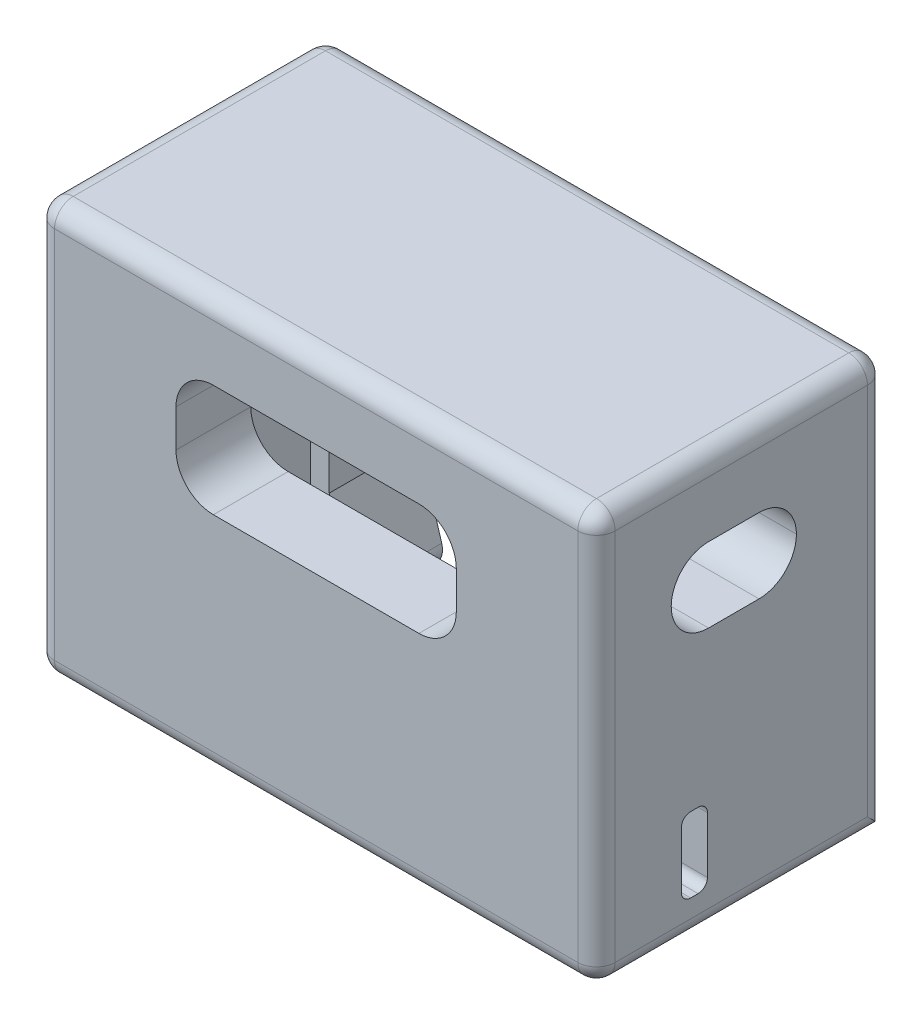
SolidWorks part; units mm, degrees
ref_plane "Front Plane" through (0, 0, 0) normal (0, 0, 1) x (1, 0, 0)
ref_plane "Top Plane" through (0, 0, 0) normal (0, 1, 0) x (1, 0, 0)
ref_plane "Right Plane" through (0, 0, 0) normal (1, 0, 0) x (0, 0, -1)
sketch "Sketch1" plane through (0, 0, 0) normal (0, 1, 0) x (1, 0, 0)
  line L1 (-19.05, 3.048) -> (19.05, 3.048)
  line L2 (-19.05, 3.048) -> (-19.05, -3.048)
  line L3 (-19.05, -3.048) -> (19.05, -3.048)
  line L4 (19.05, 3.048) -> (19.05, -3.048)
  line L5 (-19.05, 3.048) -> (19.05, -3.048) construction
  line L6 (-19.05, -3.048) -> (19.05, 3.048) construction
  point P0 (0, 0)
  dimension "D1" = 38.1
  dimension "D2" = 6.096
extrude "Boss-Extrude1" add sketch "Sketch1" along normal blind 22.86
sketch "Sketch4" plane through (0, 0, 0) normal (0, -1, 0) x (1, 0, 0)
  line L0 (19.05, -3.048) -> (-19.05, -3.048) construction
  line L1 (-12.7, 3.048) -> (12.7, 3.048)
  line L2 (-12.7, 3.048) -> (-12.7, -3.048)
  line L3 (-12.7, -3.048) -> (12.7, -3.048)
  line L4 (12.7, 3.048) -> (12.7, -3.048)
  line L5 (-12.7, 3.048) -> (12.7, -3.048) construction
  line L6 (-12.7, -3.048) -> (12.7, 3.048) construction
  point P0 (0, 0)
  dimension "D1" = 25.4
extrude "Cut-Extrude1" cut sketch "Sketch4" against normal blind 15.875
fillet "Fillet1" radius 1.27 1 edges at (0, 15.875, -3.048)
sketch "Sketch5" plane through (0, 22.86, 0) normal (0, 1, 0) x (1, 0, 0)
  line L1 (19.05, 3.048) -> (-19.05, 3.048)
  line L2 (19.05, 3.048) -> (19.05, -16.637)
  line L3 (19.05, -16.637) -> (-19.05, -16.637)
  line L4 (-19.05, 3.048) -> (-19.05, -16.637)
  dimension "D1" = 19.685
  dimension "D2" = 38.1
extrude "Boss-Extrude2" add sketch "Sketch5" along normal blind 5.08
sketch "Sketch6" plane through (0, 0, 3.048) normal (0, 0, 1) x (1, 0, 0)
  line L0 (-12.7, 0) -> (-10.668, 0)
  line L1 (-10.668, 0) -> (-12.7, 6.858)
  line L2 (-12.7, 15.875) -> (-12.7, 0) construction
  line L3 (-12.7, 6.858) -> (-12.7, 0)
  dimension "D1" = 2.032
  dimension "D2" = 6.858
extrude "Boss-Extrude3" add sketch "Sketch6" against normal up to surface (6.096 mm away) up to face at (0, 11.2713, -3.048)
sketch "Sketch7" plane through (0, 0, 3.048) normal (0, 0, 1) x (1, 0, 0)
  line L0 (12.7, 0) -> (10.668, 0)
  line L1 (10.668, 0) -> (12.7, 6.858)
  line L2 (12.7, 15.875) -> (12.7, 0) construction
  line L3 (12.7, 6.858) -> (12.7, 0)
  dimension "D1" = 2.032
  dimension "D2" = 6.858
extrude "Boss-Extrude4" add sketch "Sketch7" against normal up to surface (6.096 mm away) up to face at (-1.1853, 10.7809, -3.048)
fillet "Fillet2" radius 1.27 2 edges at (10.668, 0, 0) (-10.668, 0, 0)
sketch "Sketch9" plane through (0, 22.86, 0) normal (0, -1, 0) x (1, 0, 0)
  line L0 (-19.05, 3.048) -> (-19.05, 16.637) construction
  line L1 (19.05, 16.637) -> (-19.05, 16.637)
  line L2 (19.05, 16.637) -> (19.05, 11.557)
  line L3 (19.05, 11.557) -> (-19.05, 11.557)
  line L4 (-19.05, 16.637) -> (-19.05, 11.557)
  dimension "D1" = 5.08
extrude "Boss-Extrude5" add sketch "Sketch9" along normal blind 22.86
sketch "Sketch10" plane through (19.05, 0, 0) normal (1, 0, 0) x (0, 0, -1)
  line L0 (-3.048, 22.86) -> (-3.048, 0) construction
  line L1 (-11.557, 0) -> (-3.048, 0)
  line L2 (-11.557, 0) -> (-11.557, 17.78)
  line L3 (-11.557, 17.78) -> (-3.048, 17.78)
  line L4 (-3.048, 0) -> (-3.048, 17.78)
  dimension "D1" = 17.78
extrude "Boss-Extrude6" add sketch "Sketch10" against normal blind 5.08
sketch "Sketch11" plane through (-19.05, 0, 0) normal (-1, 0, 0) x (0, 0, 1)
  line L0 (11.557, 0) -> (11.557, 22.86) construction
  line L1 (3.048, 0) -> (11.557, 0)
  line L2 (3.048, 0) -> (3.048, 17.78)
  line L3 (3.048, 17.78) -> (11.557, 17.78)
  line L4 (11.557, 0) -> (11.557, 17.78)
  dimension "D1" = 17.78
extrude "Boss-Extrude7" add sketch "Sketch11" against normal blind 5.08
sketch "Sketch12" plane through (0, 0, 16.637) normal (0, 0, 1) x (1, 0, 0)
  line L0 (-19.05, 22.86) -> (19.05, 22.86) construction
  line L1 (-9.525, 22.86) -> (9.525, 22.86)
  line L2 (-9.525, 22.86) -> (-9.525, 15.24)
  line L3 (-9.525, 15.24) -> (9.525, 15.24)
  line L4 (9.525, 22.86) -> (9.525, 15.24)
  line L5 (-9.525, 22.86) -> (9.525, 15.24) construction
  line L6 (-9.525, 15.24) -> (9.525, 22.86) construction
  point P0 (0, 19.05)
  dimension "D1" = 3.81
  dimension "D2" = 7.62
  dimension "D3" = 19.05
extrude "Cut-Extrude2" cut sketch "Sketch12" against normal up to surface (5.08 mm away) up to face at (0, 14.605, 11.557)
fillet "Fillet3" radius 2.54 4 edges at (9.525, 22.86, 14.097) (-9.525, 22.86, 14.097) (-9.525, 15.24, 14.097) (9.525, 15.24, 14.097)
fillet "Fillet5" radius 2.54 7 edges at (13.0175, 22.86, 11.557) (16.51, 17.78, 11.557) (16.51, 17.78, 3.048) (0, 22.86, 3.048) (-13.0175, 22.86, 11.557) (-16.51, 17.78, 11.557) (-16.51, 17.78, 3.048)
fillet "Fillet6" radius 1.27 11 edges at (19.05, 0, 6.7945) (-19.05, 0, 6.7945) (0, 0, 16.637) (-19.05, 13.97, 16.637) (-19.05, 13.97, -3.048) (19.05, 13.97, -3.048) (19.05, 13.97, 16.637) (19.05, 27.94, 6.7945) (-19.05, 27.94, 6.7945) (0, 27.94, 16.637) (0, 27.94, -3.048)
sketch "Sketch13" plane through (0, 22.86, 0) normal (0, -1, 0) x (1, 0, 0)
  line L0 (-19.05, 5.588) -> (19.05, 5.588) construction
  line L1 (-6.985, 9.017) -> (6.9558, 9.017)
  line L2 (-6.985, 9.017) -> (-6.985, 5.588)
  line L3 (-6.985, 5.588) -> (6.9558, 5.588)
  line L4 (6.9558, 9.017) -> (6.9558, 5.588)
extrude "Boss-Extrude8" add sketch "Sketch13" along normal blind 1.524
sketch "Sketch22" plane through (19.05, 0, 0) normal (1, 0, 0) x (0, 0, -1)
  line L1 (-10.872, 2.5034) -> (-9.094, 2.5034)
  line L2 (-10.872, 2.5034) -> (-10.872, 7.5834)
  line L3 (-10.872, 7.5834) -> (-9.094, 7.5834)
  line L4 (-9.094, 2.5034) -> (-9.094, 7.5834)
  dimension "D1" = 1.778
  dimension "D2" = 5.08
extrude "Cut-Extrude5" cut sketch "Sketch22" against normal up to surface (38.1 mm away) up to face at (-19.05, 13.97, 6.7945)
fillet "Fillet7" radius 0.635 8 edges at (-16.51, 7.5834, 9.094) (-16.51, 7.5834, 10.872) (-16.51, 2.5034, 10.872) (-16.51, 2.5034, 9.094) (16.51, 2.5034, 9.094) (16.51, 7.5834, 9.094) (16.51, 7.5834, 10.872) (16.51, 2.5034, 10.872)
